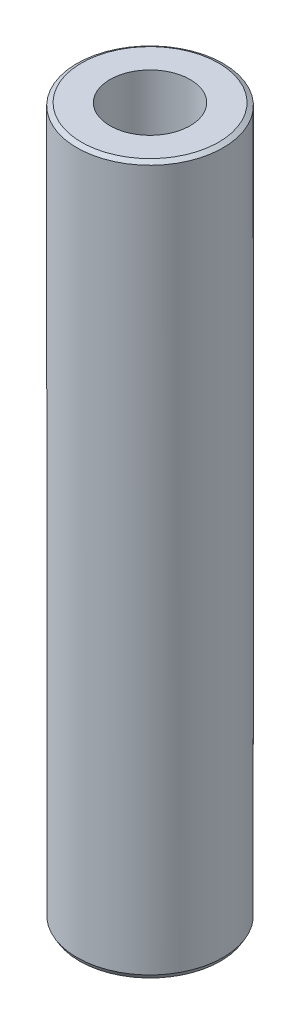
SolidWorks part; units mm, degrees
ref_plane "Front Plane" through (0, 0, 0) normal (0, 0, 1) x (1, 0, 0)
ref_plane "Top Plane" through (0, 0, 0) normal (0, 1, 0) x (1, 0, 0)
ref_plane "Right Plane" through (0, 0, 0) normal (1, 0, 0) x (0, 0, -1)
sketch "Sketch1" plane through (0, 0, 0) normal (0, 1, 0) x (1, 0, 0)
  circle A0 centre (0, 0) radius 60
  dimension "SHAFT_OD" = 120
extrude "Boss-Extrude1" add sketch "Sketch1" along normal blind 581.3993
sketch "Sketch2" plane through (0, 0, 0) normal (0, 1, 0) x (1, 0, 0)
  circle A0 centre (0, 0) radius 32.9151
  dimension "BORE_D" = 65.8302
extrude "Cut-Extrude1" cut sketch "Sketch2" along normal through all
chamfer "Chamfer1" distance 2.1275 angle 60 2 edges at (0, 581.3993, 60) (0, 0, 60) first distance on face at (0, 581.3993, 60) first distance on face at (0, 0, 32.9151)
